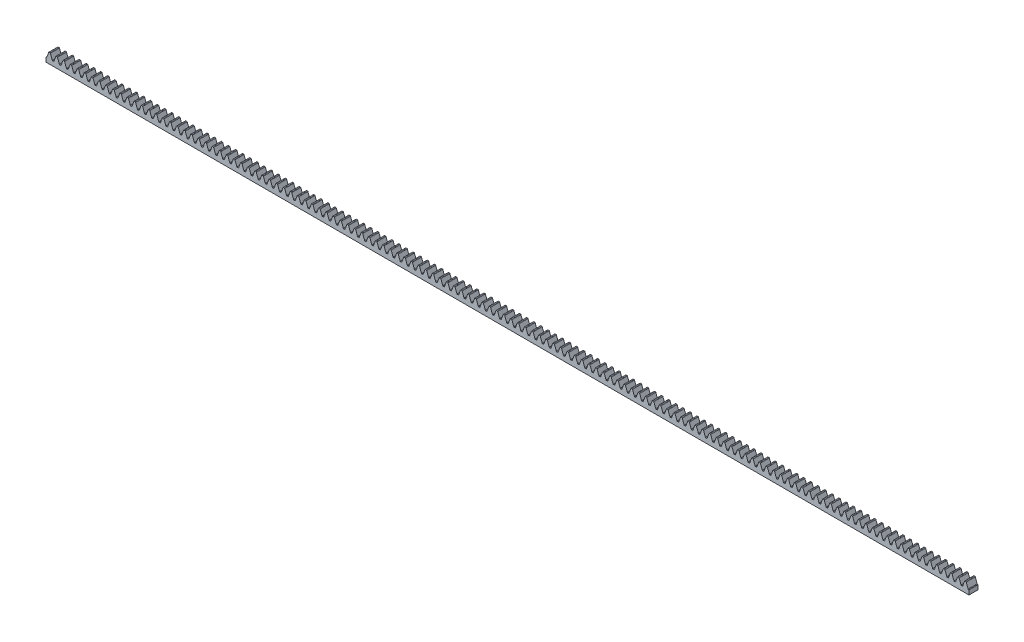
SolidWorks part; units mm, degrees
material "Acrylic (Medium-high impact)"
ref_plane "Front Plane" through (0, 0, 0) normal (0, 0, 1) x (1, 0, 0)
ref_plane "Top Plane" through (0, 0, 0) normal (0, 1, 0) x (1, 0, 0)
ref_plane "Right Plane" through (0, 0, 0) normal (1, 0, 0) x (0, 0, -1)
sketch "Sketch1" plane through (0, 0, 0) normal (0, 0, 1) x (1, 0, 0)
  line L0 (-3.927, 0) -> (3.927, 0)
  line L1 (3.927, 0) -> (3.927, 5)
  line L2 (3.927, 5) -> (3.451, 5)
  line L3 (2.9812, 5.329) -> (0.9458, 10.921)
  line L4 (0.476, 11.25) -> (-0.476, 11.25)
  line L5 (0, -5.5203) -> (0, 27.1646) construction
  line L6 (0, 8.125) -> (1.9635, 8.125) construction
  line L7 (-3.927, 0) -> (-3.927, 5)
  line L8 (-3.927, 5) -> (-3.451, 5)
  line L9 (-2.9812, 5.329) -> (-0.9458, 10.921)
  arc A0 (-0.9458, 10.921) -> (-0.476, 11.25) centre (-0.476, 10.75) cw
  arc A1 (0.9458, 10.921) -> (0.476, 11.25) centre (0.476, 10.75) ccw
  arc A2 (3.451, 5) -> (2.9812, 5.329) centre (3.451, 5.5) cw
  arc A3 (-2.9812, 5.329) -> (-3.451, 5) centre (-3.451, 5.5) cw
  point P13 (0, 0)
  point P16 (0, 11.25)
  point P17 (-0.8261, 11.25)
  point P20 (0.8261, 11.25)
  point P23 (3.1009, 5)
  point P26 (-3.1009, 5)
  dimension "D7" = 0.5
  dimension "D1" = 3.125
  dimension "D2" = 3.125
  dimension "D3" = 110
  dimension "D4" = 5
  dimension "D5" = 3.927
  dimension "D6" = 1.9635
extrude "Boss-Extrude1" add sketch "Sketch1" along normal blind 10
pattern_linear "LPattern2" count 130 spacing 7.854 along (-1, 0, 0) of "Boss-Extrude1"
equation "\"m\"= 2.5'module"
equation "\"phi\"= 20'pressure angle"
equation "\"a\"= 1.25 * \"m\"'addendum"
equation "\"b\"= \"m\"'deddendum"
equation "\"c\"= \"a\" - \"b\"'clearance"
equation "\"pc\"= pi * \"m\"'circular pitch"
equation "\"D1@Sketch1\" = \"b\" + \"c\"'deddendum"
equation "\"D2@Sketch1\" = \"a\"'addendum"
equation "\"D6@Sketch1\" = \"pc\" / 4 "
equation "\"D5@Sketch1\"  = \"pc\" / 2"
equation "\"D7@Sketch1\" = 0.8 * \"c\"'fillet radius"
